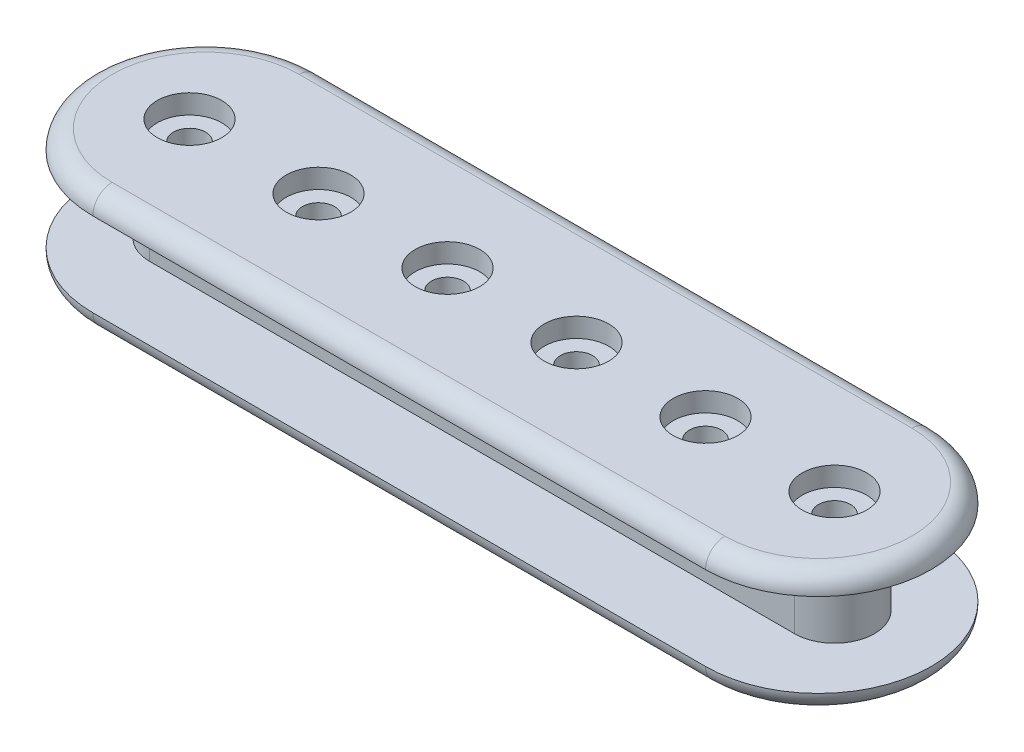
SolidWorks part; units mm, degrees
material "ABS"
ref_plane "Front Plane" through (0, 0, 0) normal (0, 0, 1) x (1, 0, 0)
ref_plane "Top Plane" through (0, 0, 0) normal (0, 1, 0) x (1, 0, 0)
ref_plane "Right Plane" through (0, 0, 0) normal (1, 0, 0) x (0, 0, -1)
sketch "Sketch1" plane through (0, 0, 0) normal (0, 1, 0) x (1, 0, 0)
  line L0 (24.13, 0) -> (-24.13, 0) construction
  line L1 (24.13, -8.89) -> (-24.13, -8.89)
  line L2 (24.13, 8.89) -> (-24.13, 8.89)
  arc A0 (24.13, -8.89) -> (24.13, 8.89) centre (24.13, 0) ccw
  arc A1 (-24.13, 8.89) -> (-24.13, -8.89) centre (-24.13, 0) ccw
  point P2 (0, 0)
  point P8 (-33.02, 0)
  point P9 (33.02, 0)
  dimension "D1" = 17.78
  dimension "D2" = 66.04
extrude "Boss-Extrude1" add sketch "Sketch1" along normal blind 1.524
sketch "Sketch2" plane through (0, 1.524, 0) normal (0, 1, 0) x (1, 0, 0)
  line L0 (-33.02, 0) -> (33.02, 0) construction
  line L1 (-25.4, 3.1496) -> (25.4, 3.1496)
  line L2 (-24.13, -8.89) -> (24.13, -8.89) construction
  line L3 (25.4, 1.524) -> (-25.4, 1.524)
  line L4 (25.4, 1.524) -> (25.4, -1.524)
  line L5 (25.4, -1.524) -> (-25.4, -1.524)
  line L6 (-25.4, 1.524) -> (-25.4, -1.524)
  line L7 (25.4, 1.524) -> (-25.4, -1.524) construction
  line L8 (25.4, -1.524) -> (-25.4, 1.524) construction
  line L9 (-25.4, -3.1496) -> (25.4, -3.1496)
  arc A0 (-24.13, 8.89) -> (-24.13, -8.89) centre (-24.13, 0) ccw construction
  arc A1 (24.13, -8.89) -> (24.13, 8.89) centre (24.13, 0) ccw construction
  circle A2 centre (-25.4, 0) radius 3.1496
  circle A3 centre (-15.24, 0) radius 3.1496
  circle A4 centre (-5.08, 0) radius 3.1496
  circle A5 centre (5.08, 0) radius 3.1496
  circle A6 centre (15.24, 0) radius 3.1496
  circle A7 centre (25.4, 0) radius 3.1496
  circle A8 centre (-25.4, 0) radius 1.27
  circle A9 centre (-15.24, 0) radius 1.27
  circle A10 centre (-5.08, 0) radius 1.27
  circle A11 centre (5.08, 0) radius 1.27
  circle A12 centre (15.24, 0) radius 1.27
  circle A13 centre (25.4, 0) radius 1.27
  point P10 (0, 0)
  point P30 (0, -8.89)
  dimension "D1" = 6.2992
  dimension "D3" = 6
  dimension "D7" = 2.54
  dimension "D2" = 7.62
  dimension "D4" = 8.89
  dimension "D5" = 7.366
  dimension "D6" = 50.8
  dimension "D8" = 6
extrude "Boss-Extrude2" add sketch "Sketch2" along normal blind 6.604 contours A8 L6 L3 A2 L5 | A3 L1 A2 L3 | A3 L3 A2 L5 | A8 L6 L5 A2 L3 | A3 L5 A2 L9 | A3 L5 | L5 A3 L3 A9 | L3 A3 | A4 L1 A3 L3 | A4 L3 A3 L5 | A4 L5 A3 L9 | A4 L5 | L5 A4 L3 A10 | L3 A4 | A5 L1 A4 L3 | A5 L3 A4 L5 | A5 L5 A4 L9 | A5 L5 | L5 A5 L3 A11 | L3 A5 | A6 L1 A5 L3 | A6 L3 A5 L5 | A6 L5 A5 L9 | A6 L5 | L5 A6 L3 A12 | L3 A6 | A7 L1 A6 L3 | A7 L5 A6 L9 | A7 L3 A6 L5 | A13 L4 L5 A7 L3 | A13 L4 L3 A7 L5 region at (-23.8439, 1.524, -2.6386) region at (-20.32, 1.524, -2.4283) region at (-10.16, 1.524, -2.4283) region at (-15.24, 1.524, -2.1912) region at (-20.32, 1.524, 2.4283) region at (-23.5172, 1.524, 0) region at (-20.32, 1.524, 0) region at (0, 1.524, -2.4283) region at (-5.08, 1.524, -2.1912) region at (-12.2581, 1.524, -0.7695) region at (-10.16, 1.524, 0) region at (-10.16, 1.524, 2.4283) region at (-15.24, 1.524, 2.1912) region at (10.16, 1.524, -2.4283) region at (5.08, 1.524, -2.1912) region at (-2.0981, 1.524, -0.7695) region at (0, 1.524, 0) region at (0, 1.524, 2.4283) region at (-5.08, 1.524, 2.1912) region at (20.32, 1.524, -2.4283) region at (15.24, 1.524, -2.1912) region at (8.0619, 1.524, -0.7695) region at (10.16, 1.524, 0) region at (10.16, 1.524, 2.4283) region at (5.08, 1.524, 2.1912) region at (27.566, 1.524, -2.166) region at (18.2219, 1.524, -0.7695) region at (20.32, 1.524, 0) region at (20.32, 1.524, 2.4283) region at (15.24, 1.524, 2.1912) region at (23.5172, 1.524, 0)
sketch "Sketch3" plane through (0, 8.128, 0) normal (0, 1, 0) x (1, 0, 0)
  line L0 (-24.13, -8.89) -> (24.13, -8.89) construction
  line L1 (24.13, 8.89) -> (-24.13, 8.89) construction
  line L2 (-24.13, -8.89) -> (24.13, -8.89)
  line L3 (24.13, 8.89) -> (-24.13, 8.89)
  arc A0 (24.13, -8.89) -> (24.13, 8.89) centre (24.13, 0) ccw construction
  arc A1 (-24.13, 8.89) -> (-24.13, -8.89) centre (-24.13, 0) ccw construction
  arc A2 (24.13, -8.89) -> (24.13, 8.89) centre (24.13, 0) ccw
  arc A3 (-24.13, 8.89) -> (-24.13, -8.89) centre (-24.13, 0) ccw
extrude "Boss-Extrude3" add sketch "Sketch3" along normal blind 1.524
fillet "Fillet1" radius 1.524 8 edges at (33.02, 0, 0) (0, 0, -8.89) (0, 0, 8.89) (-33.02, 0, 0) (33.02, 9.652, 0) (0, 9.652, 8.89) (0, 9.652, -8.89) (-33.02, 9.652, 0)
extrude "Cut-Extrude1" cut sketch "Sketch2<3>" against normal through all both and the other way through all contours A8 | A9 | A10 | A11 | A12 | A13
sketch "Sketch2<3>" plane through (0, 1.524, 0) normal (0, 1, 0) x (1, 0, 0) same geometry as "Sketch2"
sketch "Sketch4" plane through (0, 9.652, 0) normal (0, 1, 0) x (1, 0, 0)
  circle A0 centre (-25.4, 0) radius 2.54
  circle A1 centre (-15.24, 0) radius 2.54
  circle A2 centre (-5.08, 0) radius 2.54
  circle A3 centre (5.08, 0) radius 2.54
  circle A4 centre (15.24, 0) radius 2.54
  circle A5 centre (25.4, 0) radius 2.54
  dimension "D1" = 5.08
  dimension "D2" = 6
extrude "Cut-Extrude2" cut sketch "Sketch4" against normal up to surface (1.524 mm away) and the other way through all up to face at (0, 8.128, 0)
